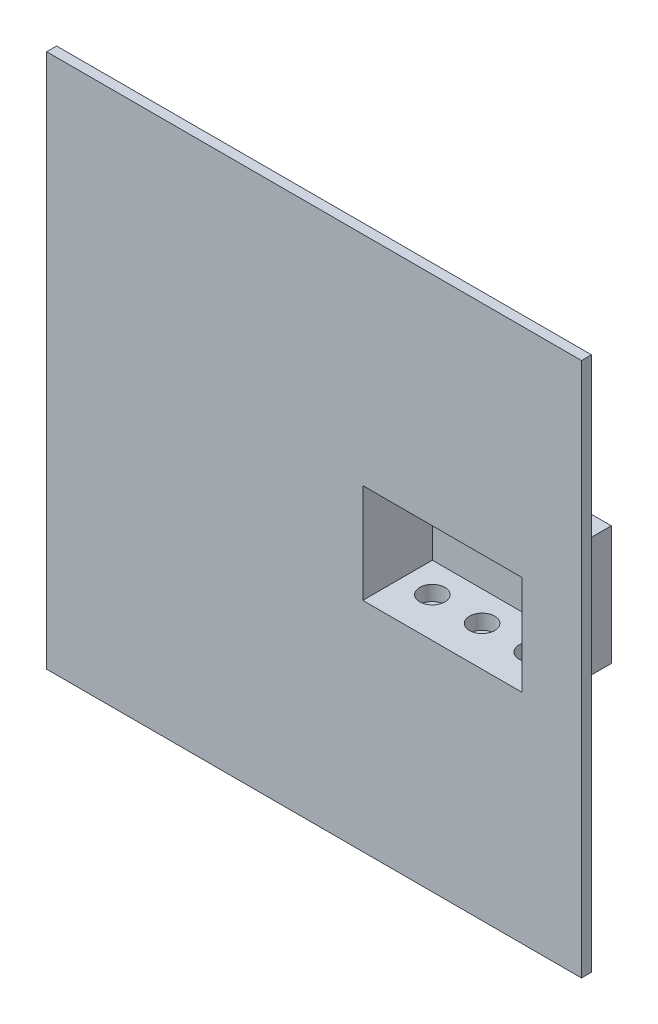
SolidWorks part; units mm, degrees
material "PE High Density Film"
ref_plane "Front Plane" through (0, 0, 0) normal (0, 0, 1) x (1, 0, 0)
ref_plane "Top Plane" through (0, 0, 0) normal (0, 1, 0) x (1, 0, 0)
ref_plane "Right Plane" through (0, 0, 0) normal (1, 0, 0) x (0, 0, -1)
sketch "Sketch1" plane through (0, 0, 0) normal (0, 0, 1) x (1, 0, 0)
  line L1 (0, 0) -> (683.26, 0)
  line L2 (0, 0) -> (0, 683.26)
  line L3 (0, 683.26) -> (683.26, 683.26)
  line L4 (683.26, 0) -> (683.26, 683.26)
  line L5 (403.86, 405.13) -> (607.06, 405.13)
  line L6 (403.86, 405.13) -> (403.86, 278.13)
  line L7 (403.86, 278.13) -> (607.06, 278.13)
  line L8 (607.06, 405.13) -> (607.06, 278.13)
  point P9 (607.06, 341.63)
  dimension "D1" = 683.26
  dimension "D2" = 76.2
  dimension "D3" = 341.63
  dimension "D4" = 127
  dimension "D5" = 203.2
extrude "Boss-Extrude1" add sketch "Sketch1" along normal blind 12.7
sketch "Sketch2" plane through (0, 278.13, 0) normal (0, 1, 0) x (1, 0, 0)
  line L1 (403.86, 0) -> (607.06, 0)
  line L2 (403.86, 0) -> (403.86, 76.2)
  line L3 (403.86, 76.2) -> (607.06, 76.2)
  line L4 (607.06, 0) -> (607.06, 76.2)
  dimension "D1" = 76.2
extrude "Boss-Extrude2" add sketch "Sketch2" against normal blind 25.4
sketch "Sketch3" plane through (0, 278.13, 0) normal (0, 1, 0) x (1, 0, 0)
  line L6 (607.06, -12.7) -> (607.06, 0)
  line L7 (607.06, 0) -> (607.06, 76.2)
  line L8 (607.06, 76.2) -> (403.86, 76.2)
  line L9 (403.86, 76.2) -> (403.86, 0)
  line L10 (403.86, 0) -> (403.86, -12.7)
  line L11 (403.86, -12.7) -> (607.06, -12.7)
  line L12 (607.06, -12.7) -> (607.06, 0)
  line L13 (607.06, 0) -> (607.06, 76.2)
  line L14 (607.06, 76.2) -> (403.86, 76.2)
  line L15 (403.86, 76.2) -> (403.86, 0)
  line L16 (403.86, 0) -> (403.86, -12.7)
  line L17 (403.86, -12.7) -> (607.06, -12.7)
  circle A1 centre (441.96, 38.1) radius 16.0655
  circle A2 centre (505.46, 38.1) radius 16.0655
  circle A3 centre (568.96, 38.1) radius 16.0655
  point P6 (403.86, 38.1)
  dimension "D2" = 32.131
  dimension "D4" = 32.131
  dimension "D5" = 32.131
  dimension "D3" = 38.1
  dimension "D6" = 63.5
  dimension "D7" = 63.5
  dimension "D1" = 0
extrude "Cut-Extrude1" cut sketch "Sketch3" against normal blind 19.05 contours A3 | A2 | A1 region at (441.96, 278.13, -38.1) region at (505.46, 278.13, -38.1) region at (568.96, 278.13, -38.1)
sketch "Sketch4" plane through (0, 0, 0) normal (0, 0, -1) x (-1, 0, 0)
  line L0 (-607.06, 278.13) -> (-403.86, 278.13) construction
  line L1 (-607.06, 278.13) -> (-619.76, 278.13)
  line L2 (-607.06, 278.13) -> (-607.06, 405.13)
  line L3 (-607.06, 405.13) -> (-619.76, 405.13)
  line L4 (-619.76, 278.13) -> (-619.76, 405.13)
  line L5 (-607.06, 405.13) -> (-403.86, 405.13)
  line L6 (-607.06, 405.13) -> (-607.06, 417.83)
  line L7 (-607.06, 417.83) -> (-403.86, 417.83)
  line L8 (-403.86, 405.13) -> (-403.86, 417.83)
  line L9 (-403.86, 405.13) -> (-391.16, 405.13)
  line L10 (-403.86, 405.13) -> (-403.86, 278.13)
  line L11 (-403.86, 278.13) -> (-391.16, 278.13)
  line L12 (-391.16, 405.13) -> (-391.16, 278.13)
  line L13 (-403.86, 405.13) -> (-403.86, 278.13) construction
  line L15 (-607.06, 405.13) -> (-403.86, 405.13) construction
  line L16 (-607.06, 405.13) -> (-619.76, 405.13)
  line L17 (-607.06, 405.13) -> (-607.06, 417.83)
  line L18 (-607.06, 417.83) -> (-619.76, 417.83)
  line L19 (-619.76, 405.13) -> (-619.76, 417.83)
  line L20 (-403.86, 405.13) -> (-391.16, 405.13)
  line L21 (-403.86, 405.13) -> (-403.86, 417.83)
  line L22 (-403.86, 417.83) -> (-391.16, 417.83)
  line L23 (-391.16, 405.13) -> (-391.16, 417.83)
  line L24 (-607.06, 278.13) -> (-619.76, 278.13)
  line L25 (-607.06, 278.13) -> (-607.06, 265.43)
  line L26 (-607.06, 265.43) -> (-619.76, 265.43)
  line L27 (-619.76, 278.13) -> (-619.76, 265.43)
  line L28 (-403.86, 278.13) -> (-391.16, 278.13)
  line L29 (-403.86, 278.13) -> (-403.86, 265.43)
  line L30 (-403.86, 265.43) -> (-391.16, 265.43)
  line L31 (-391.16, 278.13) -> (-391.16, 265.43)
  line M7 (-403.86, 278.13) -> (-403.86, 252.73)
  line M9 (-607.06, 252.73) -> (-607.06, 278.13)
  line M10 (-607.06, 278.13) -> (-607.06, 405.13)
  line M11 (-607.06, 405.13) -> (-403.86, 405.13)
  line M12 (-403.86, 405.13) -> (-403.86, 278.13)
  dimension "D1" = 12.7
  dimension "D2" = 12.7
  dimension "D3" = 12.7
extrude "Boss-Extrude4" add sketch "Sketch4" along normal up to surface (76.2 mm away) contours L1 L27 L26 M9 | L4 L1 L3 M10 | L8 L7 L6 M11 | L19 L3 L6 L18 | L9 L23 L22 L8 | L12 L9 L11 M12 | L31 L11 L30 M7 region at (613.41, 271.78, 0) region at (613.41, 341.63, 0) region at (505.46, 411.48, 0) region at (613.41, 411.48, 0) region at (397.51, 411.48, 0) region at (397.51, 341.63, 0) region at (397.51, 271.78, 0) up to face at (505.46, 265.43, -76.2)
sketch "Sketch5" plane through (0, 0, -76.2) normal (0, 0, -1) x (-1, 0, 0)
  line L4 (-607.06, 252.73) -> (-403.86, 252.73)
  line L5 (-391.16, 265.43) -> (-391.16, 417.83)
  line L6 (-391.16, 417.83) -> (-619.76, 417.83)
  line L7 (-619.76, 417.83) -> (-619.76, 265.43)
  line L8 (-607.06, 252.73) -> (-403.86, 252.73)
  line L9 (-391.16, 265.43) -> (-391.16, 417.83)
  line L10 (-391.16, 417.83) -> (-619.76, 417.83)
  line L11 (-619.76, 417.83) -> (-619.76, 265.43)
  line L16 (-403.86, 252.73) -> (-403.86, 265.43)
  line L17 (-403.86, 252.73) -> (-403.86, 265.43)
  line L18 (-403.86, 265.43) -> (-391.16, 265.43)
  line L19 (-403.86, 265.43) -> (-391.16, 265.43)
  line L20 (-619.76, 265.43) -> (-607.06, 265.43)
  line L21 (-619.76, 265.43) -> (-607.06, 265.43)
  line L22 (-607.06, 265.43) -> (-607.06, 252.73)
  line L23 (-607.06, 265.43) -> (-607.06, 252.73)
  dimension "D1" = 0
extrude "Boss-Extrude5" add sketch "Sketch5" along normal blind 12.7
